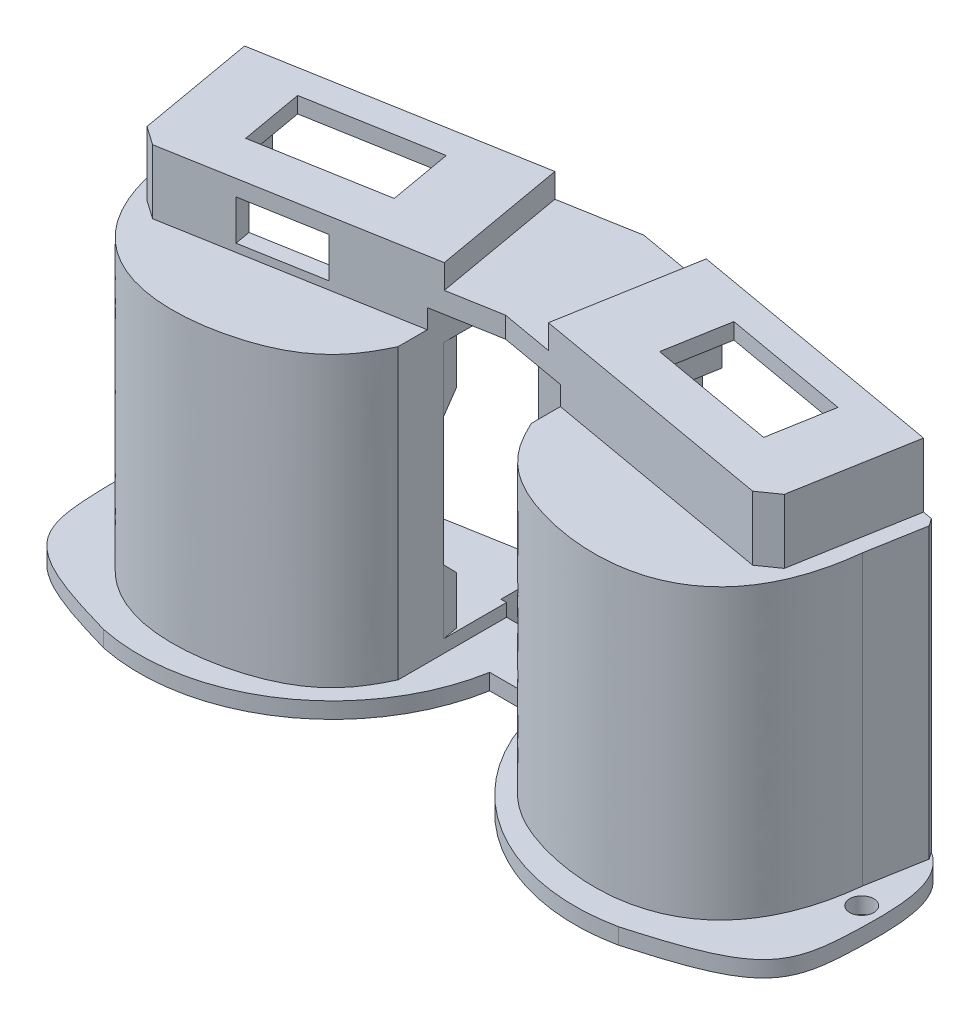
SolidWorks part; units mm, degrees
ref_plane "Front" through (0, 0, 0) normal (0, 0, 1) x (1, 0, 0)
ref_plane "Top" through (0, 0, 0) normal (0, 1, 0) x (1, 0, 0)
ref_plane "Right" through (0, 0, 0) normal (1, 0, 0) x (0, 0, -1)
sketch "草图1" plane through (0, 0, 0) normal (0, 1, 0) x (1, 0, 0)
  line L0 (-19.1474, 0) -> (24.6079, 0) construction
  line L1 (0, 18.5446) -> (0, -20.1047) construction
  line L2 (2.5, 0) -> (19.2417, -2.952)
  line L3 (19.2417, -2.952) -> (16.2897, -19.6938) construction
  line L4 (17.6789, -11.8153) -> (24.5726, -13.0308) construction
  line L5 (-2.5, 0) -> (-19.2417, -2.952)
  arc A0 (16.2897, -19.6938) -> (2.5, 0) centre (13.5849, -6.913) cw
  arc A1 (-16.2897, -19.6938) -> (-2.5, 0) centre (-13.5849, -6.913) ccw
  spline S0 degree 3 poles (16.2897, -19.6938) (21.1298, -18.3094) (24.3655, -17.0369) (24.9303, -7.3751) (24.2805, -3.9218) (19.2417, -2.952) knots 0 0 0 0 0.384247 0.484247 1 1 1 1
  spline S1 degree 3 poles (-16.2897, -19.6938) (-21.1298, -18.3094) (-24.3655, -17.0369) (-24.9303, -7.3751) (-24.2805, -3.9218) (-19.2417, -2.952) knots 0 0 0 0 0.384247 0.484247 1 1 1 1
  dimension "D1" = 17
  dimension "D2" = 17
  dimension "D3" = 10
  dimension "D4" = 2.5
  dimension "D5" = 8
  dimension "D6" = 7
extrude "凸台-拉伸1" add sketch "草图1" along normal blind 1
ref_plane "左右对称面" through (0, 0, 0) normal (1, 0, 0) x (0, 0, -1)
fillet "圆角1" radius 2 1 edges at (-2.5, 0.5, 0)
fillet "圆角2" radius 2 1 edges at (2.5, 0.5, 0)
sketch "草图6" plane through (0, 0, 0) normal (0, 1, 0) x (1, 0, 0)
  line L0 (0, 8.4586) -> (0, -23.7271) construction
  line L2 (3, -10) -> (-3, -10)
  line L3 (3, -10) -> (3, -2)
  line L4 (3, -2) -> (-3, -2)
  line L5 (-3, -10) -> (-3, -2)
  line L6 (3, -10) -> (-3, -2) construction
  line L7 (3, -2) -> (-3, -10) construction
  point P3 (0, -6)
  dimension "D1" = 6
  dimension "D2" = 8
  dimension "D3" = 6
extrude "凸台-拉伸2" add sketch "草图6" along normal blind 1
sketch "草图15" plane through (0, 1, 0) normal (0, 1, 0) x (1, 0, 0)
  line L0 (0, 13.8527) -> (0, -25.0122) construction
  line L1 (0, -1.0823) -> (22.1582, -4.9894)
  line L2 (19.2417, -2.952) -> (3.9135, -0.2492) construction
  line L3 (22.1582, -4.9894) -> (21.4636, -8.9286)
  line L4 (2.9544, -7.6958) -> (0, -7.1749)
  line L5 (-2.9544, -7.6958) -> (0, -7.1749)
  line L6 (-22.1582, -4.9894) -> (-21.4636, -8.9286)
  line L7 (0, -1.0823) -> (-22.1582, -4.9894)
  spline S0 degree 3 poles (21.4636, -8.9286) (20.459, -18.1006) (6.6127, -17.8068) (4.5456, -13.167) (2.8294, -9.2954) (2.745, -8.5011) (2.9544, -7.6958) knots 0 0 0 0 0.355715 0.690614 0.755042 1 1 1 1
  spline S1 degree 3 poles (-21.4636, -8.9286) (-20.459, -18.1006) (-6.6127, -17.8068) (-4.5456, -13.167) (-2.8294, -9.2954) (-2.745, -8.5011) (-2.9544, -7.6958) knots 0 0 0 0 0.355715 0.690614 0.755042 1 1 1 1
  dimension "D1" = 1.5
  dimension "D2" = 22.5
  dimension "D3" = 4
  dimension "D4" = 6
  dimension "D5" = 3
extrude "凸台-拉伸4" add sketch "草图15" along normal blind 18
sketch "草图16" plane through (0, 19, 0) normal (0, 1, 0) x (1, 0, 0)
  line L0 (0, 10.4547) -> (0, -22.5472) construction
  line L1 (0, -1.0823) -> (21.1734, -4.8158)
  line L2 (21.1734, -4.8158) -> (19.6974, -13.1866)
  line L7 (21.4636, -8.9286) -> (22.1582, -4.9894) construction
  line L9 (-21.1734, -4.8158) -> (-19.6974, -13.1866)
  line L10 (0, -1.0823) -> (-21.1734, -4.8158)
  line L12 (-19.6974, -13.1866) -> (0, -9.7134)
  line L13 (0, -9.7134) -> (19.6974, -13.1866)
  dimension "D1" = 1
  dimension "D2" = 8.5
extrude "凸台-拉伸5" add sketch "草图16" along normal blind 4
sketch "草图17" plane through (0, 23, 0) normal (0, 1, 0) x (1, 0, 0)
  line L0 (0, 7.4948) -> (0, -12.0891) construction
  line L1 (0, -1.0823) -> (4.7206, -1.9147)
  line L2 (22.1582, -4.9894) -> (1.7459, -1.3902) construction
  line L8 (0, -1.0823) -> (-4.7206, -1.9147)
  line L10 (-19.6974, -13.1866) -> (-3.2886, -10.2933) construction
  line L11 (-3.2446, -10.2856) -> (0, -9.7134)
  line L12 (-19.6974, -13.1866) -> (0, -9.7134) construction
  line L14 (0, -9.7134) -> (19.6974, -13.1866) construction
  line L15 (3.2446, -10.2856) -> (0, -9.7134)
  line L16 (-4.7206, -1.9147) -> (-3.2446, -10.2856)
  line L17 (4.7206, -1.9147) -> (3.2446, -10.2856)
extrude "切除-拉伸8" cut sketch "草图17" against normal blind 1.5
ref_plane "基准面1" through (0, 0, 5) normal (0, 0, 1) x (1, 0, 0)
sketch "草图24" plane through (0, 0, 5) normal (0, 0, 1) x (1, 0, 0)
  line L0 (0, 30.5033) -> (0, -8.405) construction
  line L2 (4.15, 1) -> (-4.15, 1)
  line L3 (4.15, 1) -> (4.15, 20.2)
  line L4 (4.15, 20.2) -> (-4.15, 20.2)
  line L5 (-4.15, 1) -> (-4.15, 20.2)
  line L6 (4.15, 1) -> (-4.15, 20.2) construction
  line L7 (4.15, 20.2) -> (-4.15, 1) construction
  line L11 (0, 1) -> (2.9544, 1) construction
  point P3 (0, 10.6)
  dimension "D1" = 8.3
  dimension "D2" = 19.2
extrude "舵机位" cut sketch "草图24" along normal blind 10
ref_plane "基准面2" through (0, 0, 0) normal (1, 0, 0) x (0, 0, -1)
sketch "草图13" plane through (0, 1, 0) normal (0, -1, 0) x (1, 0, 0)
  line L0 (0, -17.2689) -> (0, 27.9362) construction
  line L1 (47.281, 10) -> (-45.8309, 10) construction
  circle A0 centre (22.5, 10) radius 0.75
  circle A1 centre (-22.5, 10) radius 0.75
  dimension "D2" = 1.5
  dimension "D1" = 10
  dimension "D3" = 45
extrude "切除-拉伸14" cut sketch "草图13" along normal blind 10
sketch "草图25" plane through (0, 0, 0) normal (0, -1, 0) x (1, 0, 0)
  line L0 (0, -4.5661) -> (0, 20.9489) construction
  line L1 (0, -55) -> (0, 55) construction
  line L2 (1.4801, 2) -> (-1.4801, 2) construction
  line L3 (4.5, 3.5) -> (-4.5, 3.5)
  line L4 (4.5, 3.5) -> (4.5, 5.5)
  line L5 (4.5, 5.5) -> (-4.5, 5.5)
  line L6 (-4.5, 3.5) -> (-4.5, 5.5)
  line L7 (4.5, 3.5) -> (-4.5, 5.5) construction
  line L8 (4.5, 5.5) -> (-4.5, 3.5) construction
  point P5 (0, 4.5)
  dimension "D1" = 9
  dimension "D2" = 2
  dimension "D3" = 1.5
sketch "草图29" plane through (0, 0, 0) normal (0, -1, 0) x (1, 0, 0)
  line L8 (1.703, 9) -> (-1.703, 9)
  line L9 (-19.0603, 3.9354) -> (-3.7399, 1.234)
  line L10 (-2.1733, 3) -> (2.1733, 3)
  line L11 (3.7399, 1.234) -> (19.0603, 3.9354)
  line L12 (1.703, 9) -> (-1.703, 9)
  line L13 (-19.0603, 3.9354) -> (-3.7399, 1.234)
  line L14 (-2.1733, 3) -> (2.1733, 3)
  line L15 (3.7399, 1.234) -> (19.0603, 3.9354)
  arc A13 (-1.703, 9) -> (-16.049, 18.7225) centre (-13.5849, 6.913) ccw
  arc A14 (-3.7399, 1.234) -> (-2.6607, 1.7946) centre (-3.5662, 2.2189) ccw
  arc A15 (-2.6607, 1.7946) -> (-2.1733, 3) centre (-13.5849, 6.913) ccw
  arc A16 (2.1733, 3) -> (2.6607, 1.7946) centre (13.5849, 6.913) ccw
  arc A17 (2.6607, 1.7946) -> (3.7399, 1.234) centre (3.5662, 2.2189) ccw
  arc A18 (16.049, 18.7225) -> (1.703, 9) centre (13.5849, 6.913) ccw
  arc A19 (-1.703, 9) -> (-16.049, 18.7225) centre (-13.5849, 6.913) ccw
  arc A20 (-3.7399, 1.234) -> (-2.6607, 1.7946) centre (-3.5662, 2.2189) ccw
  arc A21 (-2.6607, 1.7946) -> (-2.1733, 3) centre (-13.5849, 6.913) ccw
  arc A22 (2.1733, 3) -> (2.6607, 1.7946) centre (13.5849, 6.913) ccw
  arc A23 (2.6607, 1.7946) -> (3.7399, 1.234) centre (3.5662, 2.2189) ccw
  arc A24 (16.049, 18.7225) -> (1.703, 9) centre (13.5849, 6.913) ccw
  spline S4 degree 3 poles (-791.3663, 2915.1113) (86.5838, -34.1407) (21.552, 31.5917) (-19.0759, 17.7802) (-19.5021, 17.6249) (-20.3362, 17.2805) (-20.7448, 17.0917) (-21.3331, 16.7593) (-21.525, 16.6401) (-21.8967, 16.3779) (-22.0773, 16.2336) (-22.4084, 15.9232) (-22.5603, 15.7562) (-22.8326, 15.3949) (-22.9539, 15.1982) (-23.2601, 14.5834) (-23.3872, 14.1475) (-23.5539, 13.2462) (-23.5969, 12.793) (-23.6562, 11.8872) (-23.6719, 11.4338) (-23.693, 10.5269) (-23.6958, 10.0731) (-23.6698, 9.1648) (-23.641, 8.7079) (-23.5224, 7.8043) (-23.4335, 7.3577) (-23.2123, 6.7065) (-23.1248, 6.4966) (-22.9148, 6.0946) (-22.7913, 5.9013) (-22.5067, 5.5418) (-22.3487, 5.3792) (-22.0051, 5.0842) (-21.8181, 4.951) (-21.2317, 4.5956) (-20.8151, 4.4186) (5.185, -4.2554) (80.5888, 109.1263) (-2091.1107, -2165.3633) knots -5.732806 -5.732806 -5.732806 -5.732806 0.125 0.125 0.1875 0.1875 0.25 0.25 0.28125 0.28125 0.3125 0.3125 0.34375 0.34375 0.375 0.375 0.4375 0.4375 0.5 0.5 0.5625 0.5625 0.625 0.625 0.6875 0.6875 0.75 0.75 0.78125 0.78125 0.8125 0.8125 0.84375 0.84375 0.875 0.875 0.9375 0.9375 4.646734 4.646734 4.646734 4.646734 only from (-16.049, 18.7225) to (-19.0603, 3.9354)
  spline S5 degree 3 poles (858.3784, -2875.3912) (-77.3924, 123.0861) (-6.4969, -4.6727) (20.5938, 4.3446) (20.8058, 4.425) (21.2222, 4.6095) (21.4276, 4.7144) (21.8172, 4.9505) (22.0024, 5.082) (22.3485, 5.3788) (22.5099, 5.5456) (22.7913, 5.9017) (22.9135, 6.0922) (23.1246, 6.496) (23.2133, 6.7093) (23.4325, 7.3549) (23.5216, 7.7998) (23.6408, 8.705) (23.6695, 9.1594) (23.6958, 10.0676) (23.693, 10.522) (23.672, 11.431) (23.6562, 11.8863) (23.5969, 12.7933) (23.5538, 13.2451) (23.4303, 13.9154) (23.3778, 14.1388) (23.2417, 14.5746) (23.159, 14.7857) (22.9575, 15.1915) (22.8374, 15.3879) (22.5628, 15.7536) (22.4102, 15.9213) (22.0797, 16.2315) (21.9008, 16.3748) (21.5278, 16.6384) (21.3354, 16.7579) (20.7458, 17.0912) (20.3368, 17.2802) (19.5026, 17.6247) (19.0767, 17.78) (-21.5473, 31.5912) (-86.418, -34.1995) (785.5463, 2916.626) knots -3.84625 -3.84625 -3.84625 -3.84625 0.0625 0.0625 0.09375 0.09375 0.125 0.125 0.15625 0.15625 0.1875 0.1875 0.21875 0.21875 0.25 0.25 0.3125 0.3125 0.375 0.375 0.4375 0.4375 0.5 0.5 0.5625 0.5625 0.59375 0.59375 0.625 0.625 0.65625 0.65625 0.6875 0.6875 0.71875 0.71875 0.75 0.75 0.8125 0.8125 0.875 0.875 6.730352 6.730352 6.730352 6.730352 only from (19.0603, 3.9354) to (16.049, 18.7225)
  spline S6 degree 3 poles (-16.049, 18.7225) (-16.92, 18.4731) (-17.7891, 18.2177) (-19.0759, 17.7802) (-19.5021, 17.6249) (-20.3362, 17.2805) (-20.7448, 17.0917) (-21.3331, 16.7593) (-21.525, 16.6401) (-21.8967, 16.3779) (-22.0773, 16.2336) (-22.4084, 15.9232) (-22.5603, 15.7562) (-22.8326, 15.3949) (-22.9539, 15.1982) (-23.2601, 14.5834) (-23.3872, 14.1475) (-23.5539, 13.2462) (-23.5969, 12.793) (-23.6562, 11.8872) (-23.6719, 11.4338) (-23.693, 10.5269) (-23.6958, 10.0731) (-23.6698, 9.1648) (-23.641, 8.7079) (-23.5224, 7.8043) (-23.4335, 7.3577) (-23.2123, 6.7065) (-23.1248, 6.4966) (-22.9148, 6.0946) (-22.7913, 5.9013) (-22.5067, 5.5418) (-22.3487, 5.3792) (-22.0051, 5.0842) (-21.8181, 4.951) (-21.2317, 4.5956) (-20.8151, 4.4186) (-19.9534, 4.1311) (-19.5084, 4.022) (-19.0603, 3.9354) knots 0 0 0 0 0.125 0.125 0.1875 0.1875 0.25 0.25 0.28125 0.28125 0.3125 0.3125 0.34375 0.34375 0.375 0.375 0.4375 0.4375 0.5 0.5 0.5625 0.5625 0.625 0.625 0.6875 0.6875 0.75 0.75 0.78125 0.78125 0.8125 0.8125 0.84375 0.84375 0.875 0.875 0.9375 0.9375 1 1 1 1
  spline S7 degree 3 poles (19.0603, 3.9354) (19.5082, 4.0219) (19.9492, 4.13) (20.5938, 4.3446) (20.8058, 4.425) (21.2222, 4.6095) (21.4276, 4.7144) (21.8172, 4.9505) (22.0024, 5.082) (22.3485, 5.3788) (22.5099, 5.5456) (22.7913, 5.9017) (22.9135, 6.0922) (23.1246, 6.496) (23.2133, 6.7093) (23.4325, 7.3549) (23.5216, 7.7998) (23.6408, 8.705) (23.6695, 9.1594) (23.6958, 10.0676) (23.693, 10.522) (23.672, 11.431) (23.6562, 11.8863) (23.5969, 12.7933) (23.5538, 13.2451) (23.4303, 13.9154) (23.3778, 14.1388) (23.2417, 14.5746) (23.159, 14.7857) (22.9575, 15.1915) (22.8374, 15.3879) (22.5628, 15.7536) (22.4102, 15.9213) (22.0797, 16.2315) (21.9008, 16.3748) (21.5278, 16.6384) (21.3354, 16.7579) (20.7458, 17.0912) (20.3368, 17.2802) (19.5026, 17.6247) (19.0767, 17.78) (17.7896, 18.2175) (16.9202, 18.4731) (16.049, 18.7225) knots 0 0 0 0 0.0625 0.0625 0.09375 0.09375 0.125 0.125 0.15625 0.15625 0.1875 0.1875 0.21875 0.21875 0.25 0.25 0.3125 0.3125 0.375 0.375 0.4375 0.4375 0.5 0.5 0.5625 0.5625 0.59375 0.59375 0.625 0.625 0.65625 0.65625 0.6875 0.6875 0.71875 0.71875 0.75 0.75 0.8125 0.8125 0.875 0.875 1 1 1 1
  dimension "D1" = 1
extrude "切除-拉伸20" cut sketch "草图29" against normal blind 1 flip side to cut
extrude "排线穿孔" cut sketch "草图25" against normal blind 18
chamfer "倒角4" distance 1 angle 45 2 edges at (19.6974, 21, 13.1866) (-19.6974, 21, 13.1866)
sketch "草图39" plane through (-0.1851, 0, 1.0497) normal (0.1736, 0, -0.9848) x (-0.9848, 0, -0.1736)
  line L0 (-22.6879, 19) -> (-22.6879, 1) construction
  line L1 (-4.6879, 1.8) -> (-21.6879, 1.8)
  line L2 (-4.6879, 1.8) -> (-4.6879, 17.8)
  line L3 (-4.6879, 17.8) -> (-21.6879, 17.8)
  line L4 (-21.6879, 1.8) -> (-21.6879, 17.8)
  line L5 (-4.6879, 1.8) -> (-21.6879, 17.8) construction
  line L6 (-4.6879, 17.8) -> (-21.6879, 1.8) construction
  line L7 (-22.2836, 1) -> (-3.0313, 1) construction
  point P0 (-13.1879, 9.8)
  dimension "D1" = 1
  dimension "D2" = 17
  dimension "D3" = 16
  dimension "D4" = 0.8
extrude "切除-拉伸28" cut sketch "草图39" against normal blind 7.5
mirror "镜向9" about plane through (0, 0, 0) normal (1, 0, 0) of "切除-拉伸28"
sketch "草图40" plane through (-0.1851, 0, 1.0497) normal (0.1736, 0, -0.9848) x (-0.9848, 0, -0.1736)
  line L0 (-5.7244, 17.8) -> (-21.6879, 17.8) construction
  line L1 (-6.1879, 17.8) -> (-20.1879, 17.8)
  line L2 (-6.1879, 17.8) -> (-6.1879, 22)
  line L3 (-6.1879, 22) -> (-20.1879, 22)
  line L4 (-20.1879, 17.8) -> (-20.1879, 22)
  line L5 (-6.1879, 17.8) -> (-20.1879, 22) construction
  line L6 (-6.1879, 22) -> (-20.1879, 17.8) construction
  line L8 (-21.6879, 23) -> (-4.9814, 23) construction
  line L9 (-13.1879, 1.8) -> (-13.1879, 35.1034) construction
  line L10 (-21.6879, 1.8) -> (-4.6879, 1.8) construction
  point P0 (-13.1879, 19.9)
  point P13 (0, 0)
  dimension "D1" = 14
  dimension "D3" = 1
extrude "切除-拉伸29" cut sketch "草图40" against normal blind 7.5
mirror "镜向10" about plane through (0, 0, 0) normal (1, 0, 0) of "切除-拉伸29"
sketch "草图43" plane through (1.4874, 0, 8.4357) normal (-0.1736, 0, -0.9848) x (-0.9848, 0, 0.1736)
  line L0 (21.6879, 4.8) -> (18.6879, 4.8)
  line L1 (21.6879, 17.8) -> (18.6879, 17.8)
  line L2 (21.6879, 17.8) -> (21.6879, 14.8)
  line L3 (21.6879, 14.8) -> (18.6879, 14.8)
  line L4 (18.6879, 17.8) -> (18.6879, 14.8)
  line L5 (21.6879, 4.8) -> (21.6879, 1.8)
  line L6 (21.6879, 1.8) -> (18.6879, 1.8)
  line L7 (18.6879, 4.8) -> (18.6879, 1.8)
  line L8 (8.7244, 4.8) -> (5.7244, 4.8)
  line L9 (8.7244, 4.8) -> (8.7244, 1.8)
  line L10 (8.7244, 1.8) -> (5.7244, 1.8)
  line L11 (5.7244, 4.8) -> (5.7244, 1.8)
  line L12 (8.7244, 17.8) -> (5.7244, 17.8)
  line L13 (8.7244, 17.8) -> (8.7244, 14.8)
  line L14 (8.7244, 14.8) -> (5.7244, 14.8)
  line L15 (5.7244, 17.8) -> (5.7244, 14.8)
  point P9 (0, 0)
  point P15 (0, 0)
  point P22 (0, 0)
  point P23 (0, 0)
  point P25 (0, 0)
  point P27 (0, 0)
  point P29 (0, 0)
  point P30 (0, 0)
  point P32 (0, 0)
  point P33 (0, 0)
  point P34 (0, 0)
  dimension "D1" = 3
  dimension "D2" = 3
  dimension "D3" = 3
  dimension "D4" = 3
  dimension "D5" = 3
  dimension "D6" = 3
  dimension "D7" = 3
  dimension "D8" = 3
extrude "凸台-拉伸10" add sketch "草图43" along normal blind 1
sketch "草图44" plane through (-1.4874, 0, 8.4357) normal (0.1736, 0, -0.9848) x (-0.9848, 0, -0.1736)
  line L0 (-20.1879, 19.5) -> (-16.1879, 19.5)
  line L1 (-21.6879, 1.8) -> (-17.6879, 1.8)
  line L2 (-21.6879, 1.8) -> (-21.6879, 4.3)
  line L3 (-21.6879, 4.3) -> (-17.6879, 4.3)
  line L4 (-17.6879, 1.8) -> (-17.6879, 4.3)
  line L5 (-20.1879, 19.5) -> (-20.1879, 22)
  line L6 (-20.1879, 22) -> (-16.1879, 22)
  line L7 (-16.1879, 19.5) -> (-16.1879, 22)
  line L8 (-10.1879, 19.5) -> (-6.1879, 19.5)
  line L9 (-10.1879, 19.5) -> (-10.1879, 22)
  line L10 (-10.1879, 22) -> (-6.1879, 22)
  line L11 (-6.1879, 19.5) -> (-6.1879, 22)
  line L12 (-9.7244, 1.8) -> (-5.7244, 1.8)
  line L13 (-9.7244, 1.8) -> (-9.7244, 4.3)
  line L14 (-9.7244, 4.3) -> (-5.7244, 4.3)
  line L15 (-5.7244, 1.8) -> (-5.7244, 4.3)
  point P17 (0, 0)
  point P19 (0, 0)
  point P21 (0, 0)
  point P23 (-16.1879, 20.75)
  point P24 (0, 0)
  dimension "D1" = 4
  dimension "D2" = 2.5
  dimension "D3" = 2.5
  dimension "D4" = 4
  dimension "D5" = 2.5
  dimension "D6" = 4
  dimension "D7" = 4
  dimension "D8" = 2.5
extrude "凸台-拉伸11" add sketch "草图44" along normal blind 1.5
sketch "草图47" plane through (-1.227, 0, 6.9585) normal (0.1736, 0, -0.9848) x (-0.9848, 0, -0.1736)
  line L0 (-8.6879, 20.6798) -> (-18.6879, 20.6798) construction
  line L3 (-13.6879, 20.6798) -> (-13.6879, -4.6997) construction
  line L9 (-21.6879, 17.8) -> (-21.6879, 1.8) construction
  circle A0 centre (-18.6879, 20.6798) radius 0.5
  circle A4 centre (-7.6879, 2.9798) radius 0.5
  circle A5 centre (-8.6879, 20.6798) radius 0.5
  circle A6 centre (-19.6879, 2.9798) radius 0.5
  point P9 (0, 0)
  point P12 (-16.7544, 2.213)
  point P14 (0, 0)
  dimension "D1" = 1
  dimension "D2" = 12
  dimension "D4" = 17.7
  dimension "D3" = 10
  dimension "D5" = 2
extrude "切除-拉伸31" cut sketch "草图47" against normal blind 2
sketch "草图48" plane through (0, 23, 0) normal (0, 1, 0) x (1, 0, 0)
  line L0 (-20.5222, -8.5088) -> (-4.0695, -5.6077) construction
  line L1 (-21.1734, -4.8158) -> (-19.871, -12.2018) construction
  line L2 (-4.7206, -1.9147) -> (-3.2446, -10.2856) construction
  line L3 (-8.2744, -8.38) -> (-16.1528, -9.7692)
  line L4 (-8.2744, -8.38) -> (-8.969, -4.4408)
  line L5 (-16.1528, -9.7692) -> (-16.8474, -5.83)
  line L6 (-8.969, -4.4408) -> (-16.8474, -5.83)
  line L7 (-8.2744, -8.38) -> (-16.8474, -5.83) construction
  line L8 (-16.1528, -9.7692) -> (-8.969, -4.4408) construction
  line L11 (-4.7206, -1.9147) -> (-21.1734, -4.8158) construction
  point P6 (0, 0)
  point P7 (-12.5609, -7.105)
  point P14 (0, 0)
  point P15 (0, 0)
  dimension "D1" = 4
  dimension "D2" = 8
extrude "切除-拉伸32" cut sketch "草图48" against normal blind 6
mirror "镜向8" about plane through (0, 0, 0) normal (1, 0, 0) of "切除-拉伸32"
sketch "草图49" plane through (1.3138, 0, 7.4509) normal (-0.1736, 0, -0.9848) x (-0.9848, 0, 0.1736)
  line L0 (13.8062, 1.8) -> (13.8062, 23.56) construction
  line L4 (18.6879, 1.8) -> (21.6879, 1.8) construction
  circle A0 centre (7.5562, 3.6) radius 0.5
  circle A1 centre (20.0562, 3.6) radius 0.5
  circle A2 centre (7.5562, 16.1) radius 0.5
  circle A3 centre (20.0562, 16.1) radius 0.5
  point P14 (0, 0)
  point P15 (0, 0)
  dimension "D1" = 1
  dimension "D2" = 1
  dimension "D3" = 12.5
  dimension "D4" = 12.5
  dimension "D5" = 1.8
  dimension "D7" = 12.5
extrude "切除-拉伸33" cut sketch "草图49" against normal blind 3
sketch "草图50" plane through (1.6611, 0, 9.4206) normal (0.1736, 0, 0.9848) x (0.9848, 0, -0.1736)
  line L0 (-16.1957, 19.5) -> (-11.1957, 19.5)
  line L1 (-16.1957, 19.5) -> (-16.1957, 22)
  line L2 (-11.1957, 19.5) -> (-11.1957, 22)
  line L3 (-16.1957, 22) -> (-11.1957, 22)
  line L4 (-16.1957, 19.5) -> (-11.1957, 22) construction
  line L5 (-11.1957, 19.5) -> (-16.1957, 22) construction
  line L6 (-20.6879, 23) -> (-4.9814, 23) construction
  point P0 (-13.6957, 19.5)
  point P1 (-13.6957, 20.75)
  dimension "D1" = 5
  dimension "D2" = 2.5
  dimension "D3" = 1
extrude "切除-拉伸34" cut sketch "草图50" against normal blind 3
chamfer "倒角6" distance 0.4 angle 45 2 edges at (22.1582, 10, 4.9894) (-22.1582, 10, 4.9894)
chamfer "倒角7" distance 1 angle 45 8 edges at (-18.3938, 14.8, 11.9413) (-5.6272, 14.8, 9.6903) (-18.3938, 4.8, 11.9413) (-5.6272, 4.8, 9.6903) (6.1196, 4.3, 9.7771) (17.9014, 4.3, 11.8545) (6.5761, 19.5, 9.8576) (16.4242, 19.5, 11.594)
